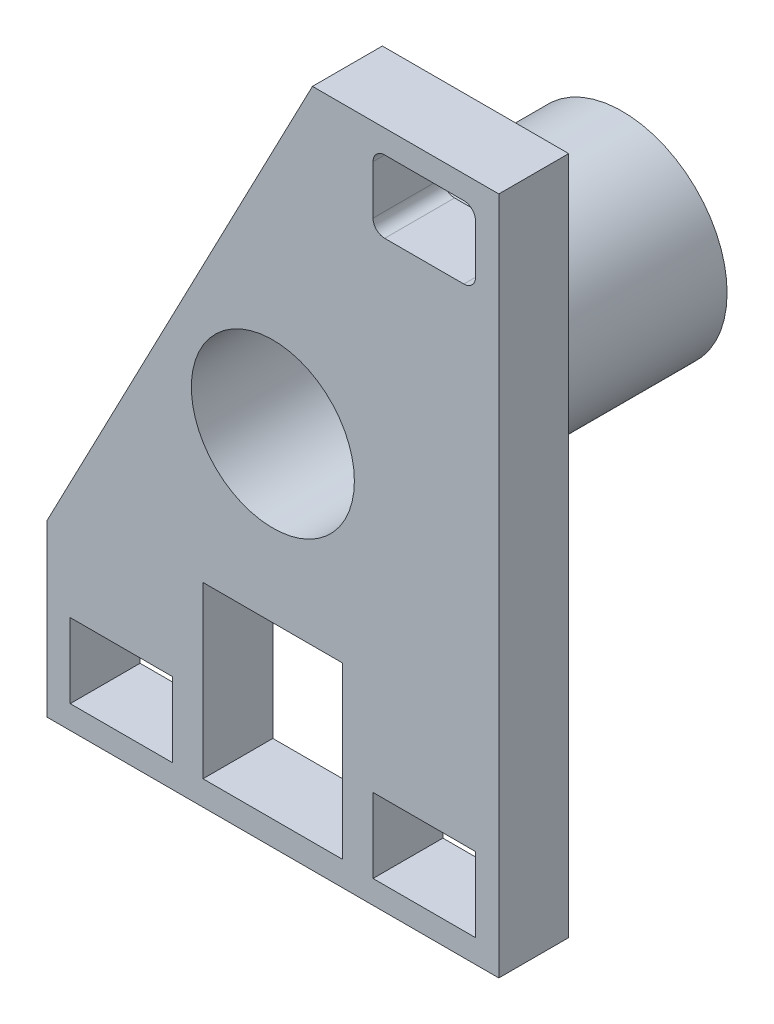
SolidWorks part; units mm, degrees
ref_plane "Front Plane" through (0, 0, 0) normal (0, 0, 1) x (1, 0, 0)
ref_plane "Top Plane" through (0, 0, 0) normal (0, 1, 0) x (1, 0, 0)
ref_plane "Right Plane" through (0, 0, 0) normal (1, 0, 0) x (0, 0, -1)
sketch "Sketch2" plane through (0, 0, 0) normal (0, 0, 1) x (1, 0, 0)
  line L0 (5.1046, -104.9632) -> (70.1046, -104.9632) construction
  line L1 (5.1046, 135.0368) -> (5.1046, -104.9632) construction
  line L2 (70.1046, -104.9632) -> (70.1046, 135.0368) construction
  line L3 (70.1046, 135.0368) -> (26.1046, 135.0368) construction
  line L4 (26.1046, 135.0368) -> (-59.8954, -32.9944) construction
  line L5 (-59.8954, -32.9944) -> (-59.8954, -104.9632) construction
  line L6 (-59.8954, -104.9632) -> (5.1046, -104.9632) construction
  line L7 (92.1046, 148.2211) -> (92.1046, -130.9632) construction
  line L8 (48.1046, 154.3078) -> (48.1046, -150.1586) construction
  line L9 (48.1046, 135.0368) -> (92.1046, 135.0368) construction
  line L10 (22.1046, 160.5368) -> (102.1046, 160.5368)
  line L11 (48.1046, 150.5368) -> (92.1046, 150.5368)
  line L12 (48.1046, 150.5368) -> (48.1046, 119.5368)
  line L13 (48.1046, 119.5368) -> (92.1046, 119.5368)
  line L14 (92.1046, 150.5368) -> (92.1046, 119.5368)
  line L15 (48.1046, 150.5368) -> (92.1046, 119.5368) construction
  line L16 (48.1046, 119.5368) -> (92.1046, 150.5368) construction
  line L17 (48.1046, -88.9632) -> (92.1046, -88.9632)
  line L18 (48.1046, -88.9632) -> (48.1046, -120.9632)
  line L19 (48.1046, -120.9632) -> (92.1046, -120.9632)
  line L20 (92.1046, -88.9632) -> (92.1046, -120.9632)
  line L21 (48.1046, -88.9632) -> (92.1046, -120.9632) construction
  line L22 (48.1046, -120.9632) -> (92.1046, -88.9632) construction
  line L23 (-81.8954, -88.9632) -> (-37.8954, -88.9632)
  line L24 (-81.8954, -88.9632) -> (-81.8954, -120.9632)
  line L25 (-81.8954, -120.9632) -> (-37.8954, -120.9632)
  line L26 (-37.8954, -88.9632) -> (-37.8954, -120.9632)
  line L27 (-81.8954, -88.9632) -> (-37.8954, -120.9632) construction
  line L28 (-81.8954, -120.9632) -> (-37.8954, -88.9632) construction
  line L29 (102.1046, 160.5368) -> (102.1046, -130.9632)
  line L30 (102.1046, -130.9632) -> (-91.8954, -130.9632)
  line L31 (-91.8954, -130.9632) -> (-91.8954, -57.9632)
  line L32 (22.1046, 160.5368) -> (-91.8954, -57.9632)
  line L34 (-24.8954, -47.396) -> (35.1046, -47.396)
  line L35 (-24.8954, -47.396) -> (-24.8954, -120.396)
  line L36 (-24.8954, -120.396) -> (35.1046, -120.396)
  line L37 (35.1046, -47.396) -> (35.1046, -120.396)
  line L38 (-24.8954, -47.396) -> (35.1046, -120.396) construction
  line L39 (-24.8954, -120.396) -> (35.1046, -47.396) construction
  circle A0 centre (5.1046, 15.0368) radius 45 construction
  point P13 (70.1046, 135.0368)
  point P30 (5.1046, -83.896)
  dimension "D7" = 90
  dimension "D8" = 10
  dimension "D1" = 240
  dimension "D2" = 130
  dimension "D3" = 44
  dimension "D4" = 31
  dimension "D5" = 32
  dimension "D6" = 44
  dimension "D9" = 10
  dimension "D10" = 10
  dimension "D11" = 10
  dimension "D12" = 73
  dimension "D13" = 60
  dimension "D14" = 80
  dimension "D15" = 73
extrude "Boss-Extrude1" add sketch "Sketch2" along normal blind 30
sketch "Sketch3" plane through (0, 0, 0) normal (0, 0, -1) x (-1, 0, 0)
  line L0 (-92.1046, 150.5368) -> (-48.1046, 150.5368) construction
  line L1 (81.8954, -88.9632) -> (81.8954, -120.9632) construction
  line L2 (-92.1046, -120.9632) -> (-92.1046, -88.9632) construction
  line L3 (-92.1046, 150.5368) -> (-48.1046, 150.5368)
  line L4 (81.8954, -88.9632) -> (81.8954, -120.9632)
  line L5 (-92.1046, -120.9632) -> (-92.1046, -88.9632)
  line L6 (-92.1046, -104.9632) -> (81.8954, -104.9632) construction
  line L7 (81.8954, -104.9632) -> (-48.1046, 150.5368) construction
  line L8 (-5.1046, 150.5368) -> (-5.1046, -104.9632) construction
  circle A0 centre (-5.1046, 22.7868) radius 45
  circle A1 centre (-5.1046, 22.7868) radius 35
  dimension "D1" = 90
  dimension "D2" = 70
extrude "Boss-Extrude2" add sketch "Sketch3" along normal blind 120 contours A1 | A0 region at (5.1046, 22.7868, 0)
fillet "Fillet1" radius 5 4 edges at (92.1046, 119.5368, 15) (48.1046, 119.5368, 15) (92.1046, 150.5368, 15) (48.1046, 150.5368, 15)
sketch "Sketch6" plane through (0, 0, 30) normal (0, 0, 1) x (1, 0, 0)
  circle A0 centre (5.1046, 22.7868) radius 35 construction
  circle A1 centre (5.1046, 22.7868) radius 35
extrude "Cut-Extrude1" cut sketch "Sketch6" against normal blind 120
fillet "Fillet2" radius 5 1 edges at (-39.8954, 22.7868, 0)
